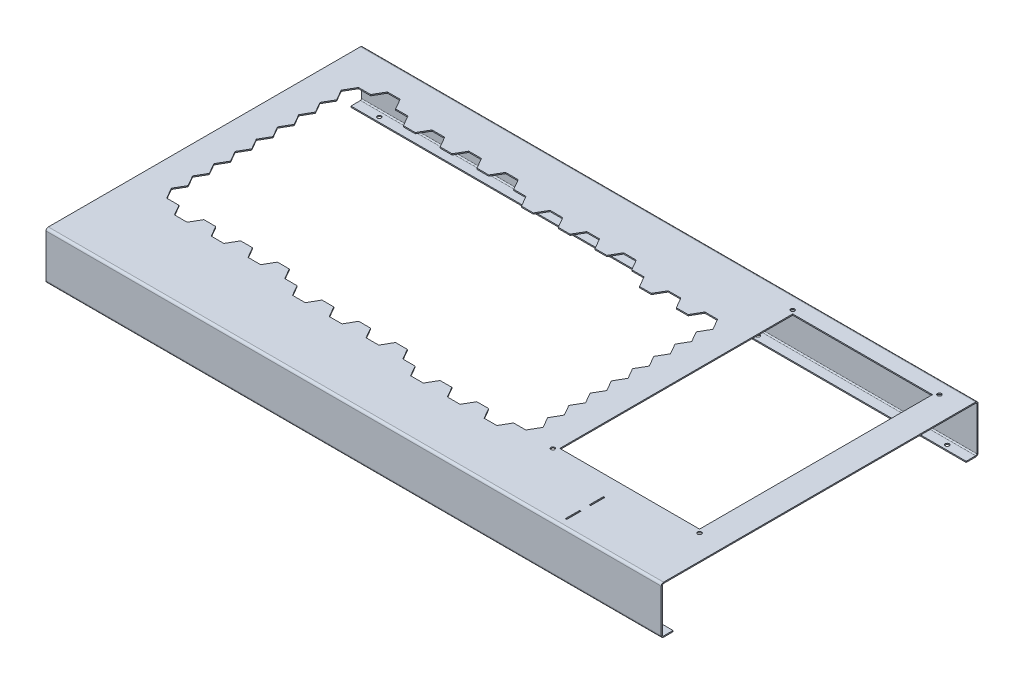
SolidWorks part; units mm, degrees
note: The reader was unsure of these and kept them because the rebuilt part matched: flange length of "Edge-Flange1", "Edge-Flange2".
ref_plane "Front" through (0, 0, 0) normal (0, 0, 1) x (1, 0, 0)
ref_plane "Top" through (0, 0, 0) normal (0, 1, 0) x (1, 0, 0)
ref_plane "Right" through (0, 0, 0) normal (1, 0, 0) x (0, 0, -1)
sketch "Sketch1" plane through (0, 0, 0) normal (0, 1, 0) x (1, 0, 0)
  line L1 (330.2, -170.0022) -> (-330.2, -170.0022)
  line L2 (330.2, -170.0022) -> (330.2, 170.0022)
  line L3 (330.2, 170.0022) -> (-330.2, 170.0022)
  line L4 (-330.2, -170.0022) -> (-330.2, 170.0022)
  line L5 (330.2, -170.0022) -> (-330.2, 170.0022) construction
  line L6 (330.2, 170.0022) -> (-330.2, -170.0022) construction
  point P0 (0, 0)
  dimension "D1" = 660.4
  dimension "D2" = 340.0044
sheet metal parameters "Sheet-Metal1" thickness 1.2192 parameters "D1"=1.27
base flange "Base-Flange1" sketch "Sketch1" thickness 1.2192 reverse thickness direction no parameters "D1"=1.27
sketch "Sketch4" plane through (0, 0, 0) normal (0, 1, 0) x (1, 0, 0)
  line L0 (114.8421, 105.8291) -> (121.6467, 94.0435)
  line L1 (121.6467, 94.0435) -> (115.0694, 82.6516)
  line L2 (94.6556, 94.4372) -> (101.2329, 105.8291)
  line L3 (101.2329, 105.8291) -> (114.8421, 105.8291)
  line L4 (115.0694, 82.6516) -> (121.6467, 71.2597)
  line L5 (121.6467, 71.2597) -> (115.0694, 59.8678)
  line L6 (115.0694, 59.8678) -> (121.6467, 48.4759)
  line L7 (121.6467, 48.4759) -> (115.0694, 37.084)
  line L8 (115.0694, 37.084) -> (121.6467, 25.6921)
  line L9 (121.6467, 25.6921) -> (115.0694, 14.3002)
  line L10 (115.0694, 14.3002) -> (121.6467, 2.9083)
  line L11 (121.6467, 2.9083) -> (115.0694, -8.4836)
  line L12 (115.0694, -8.4836) -> (121.6467, -19.8755)
  line L13 (121.6467, -19.8755) -> (115.0694, -31.2674)
  line L14 (115.0694, -31.2674) -> (121.6467, -42.6593)
  line L15 (121.6467, -42.6593) -> (115.0694, -54.0512)
  line L16 (121.6467, -65.4431) -> (115.0694, -76.835)
  line L17 (115.0694, -54.0512) -> (121.6467, -65.4431)
  line L18 (115.0694, -76.835) -> (121.6467, -88.2269)
  line L19 (121.6467, -88.2269) -> (114.8421, -100.0125)
  line L20 (114.8421, -100.0125) -> (101.6874, -100.0125)
  line L21 (101.6874, -100.0125) -> (95.1101, -111.4044)
  line L22 (95.1101, -111.4044) -> (81.5009, -111.4044)
  line L23 (81.5009, -111.4044) -> (74.9236, -100.0125)
  line L24 (74.9236, -100.0125) -> (62.2235, -100.0125)
  line L25 (62.2235, -100.0125) -> (55.6462, -111.4044)
  line L26 (55.6462, -111.4044) -> (42.037, -111.4044)
  line L27 (42.037, -111.4044) -> (35.4596, -100.0125)
  line L28 (35.4596, -100.0125) -> (22.7595, -100.0125)
  line L29 (16.1822, -111.4044) -> (2.573, -111.4044)
  line L30 (2.573, -111.4044) -> (-4.0043, -100.0125)
  line L31 (22.7595, -100.0125) -> (16.1822, -111.4044)
  line L32 (-4.0043, -100.0125) -> (-17.159, -100.0125)
  line L33 (-17.159, -100.0125) -> (-23.7363, -88.6206)
  line L34 (-23.7363, -88.6206) -> (-36.4365, -88.6206)
  line L35 (-43.0138, -100.0125) -> (-56.623, -100.0125)
  line L36 (-56.623, -100.0125) -> (-63.2003, -88.6206)
  line L37 (-36.4365, -88.6206) -> (-43.0138, -100.0125)
  line L38 (-63.2003, -88.6206) -> (-75.9005, -88.6206)
  line L39 (-82.4778, -100.0125) -> (-96.087, -100.0125)
  line L40 (-96.087, -100.0125) -> (-102.6643, -88.6206)
  line L41 (-75.9005, -88.6206) -> (-82.4778, -100.0125)
  line L42 (-121.9418, -100.0125) -> (-135.551, -100.0125)
  line L43 (-135.551, -100.0125) -> (-142.1283, -88.6206)
  line L44 (-115.3644, -88.6206) -> (-121.9418, -100.0125)
  line L45 (-142.1283, -88.6206) -> (-155.2829, -88.6206)
  line L46 (-155.2829, -88.6206) -> (-161.8603, -77.2287)
  line L47 (-161.8603, -77.2287) -> (-174.5604, -77.2287)
  line L48 (-181.1377, -88.6206) -> (-194.7469, -88.6206)
  line L49 (-194.7469, -88.6206) -> (-201.3242, -77.2287)
  line L50 (-174.5604, -77.2287) -> (-181.1377, -88.6206)
  line L51 (-201.3242, -77.2287) -> (-214.0244, -77.2287)
  line L52 (-220.6017, -88.6206) -> (-234.2109, -88.6206)
  line L53 (-234.2109, -88.6206) -> (-240.7882, -77.2287)
  line L54 (-214.0244, -77.2287) -> (-220.6017, -88.6206)
  line L55 (-240.7882, -77.2287) -> (-253.4884, -77.2287)
  line L56 (-260.0657, -88.6206) -> (-273.6749, -88.6206)
  line L57 (-273.6749, -88.6206) -> (-280.2522, -77.2287)
  line L58 (-253.4884, -77.2287) -> (-260.0657, -88.6206)
  line L59 (-280.2522, -77.2287) -> (-293.398, -77.2287)
  line L60 (-293.398, -77.2287) -> (-300.2026, -65.4431)
  line L61 (-300.2026, -65.4431) -> (-293.6253, -54.0512)
  line L62 (-293.6253, -54.0512) -> (-300.2026, -42.6593)
  line L63 (-300.2026, -42.6593) -> (-293.6253, -31.2674)
  line L64 (-293.6253, -31.2674) -> (-300.2026, -19.8755)
  line L65 (-300.2026, -19.8755) -> (-293.6253, -8.4836)
  line L66 (-300.2026, 2.9083) -> (-293.6253, 14.3002)
  line L67 (-293.6253, -8.4836) -> (-300.2026, 2.9083)
  line L68 (-293.6253, 14.3002) -> (-300.2026, 25.6921)
  line L69 (-300.2026, 25.6921) -> (-293.6253, 37.084)
  line L70 (-293.6253, 37.084) -> (-300.2026, 48.4759)
  line L71 (-300.2026, 48.4759) -> (-293.6253, 59.8678)
  line L72 (-293.6253, 59.8678) -> (-300.2026, 71.2597)
  line L73 (-300.2026, 71.2597) -> (-293.6253, 82.6516)
  line L74 (-293.6253, 82.6516) -> (-300.2026, 94.0435)
  line L75 (-300.2026, 94.0435) -> (-293.6253, 105.4354)
  line L76 (-293.6253, 105.4354) -> (-300.2026, 116.8273)
  line L77 (-300.2026, 116.8273) -> (-293.398, 128.6129)
  line L78 (-293.398, 128.6129) -> (-280.2522, 128.6129)
  line L79 (-273.6749, 140.0048) -> (-260.0657, 140.0048)
  line L80 (-260.0657, 140.0048) -> (-253.4884, 128.6129)
  line L81 (-280.2522, 128.6129) -> (-273.6749, 140.0048)
  line L82 (-253.4884, 128.6129) -> (-240.3337, 128.6129)
  line L83 (-240.3337, 128.6129) -> (-233.7564, 117.221)
  line L84 (-233.7564, 117.221) -> (-221.0562, 117.221)
  line L85 (-214.4789, 128.6129) -> (-200.8697, 128.6129)
  line L86 (-200.8697, 128.6129) -> (-194.2924, 117.221)
  line L87 (-221.0562, 117.221) -> (-214.4789, 128.6129)
  line L88 (-194.2924, 117.221) -> (-181.5922, 117.221)
  line L89 (-175.0149, 128.6129) -> (-161.4057, 128.6129)
  line L90 (-161.4057, 128.6129) -> (-154.8284, 117.221)
  line L91 (-181.5922, 117.221) -> (-175.0149, 128.6129)
  line L92 (-154.8284, 117.221) -> (-142.1283, 117.221)
  line L93 (-135.551, 128.6129) -> (-121.9418, 128.6129)
  line L94 (-121.9418, 128.6129) -> (-115.3644, 117.221)
  line L95 (-142.1283, 117.221) -> (-135.551, 128.6129)
  line L96 (-115.3644, 117.221) -> (-102.2098, 117.221)
  line L97 (-102.2098, 117.221) -> (-95.6325, 105.8291)
  line L98 (-95.6325, 105.8291) -> (-82.9323, 105.8291)
  line L99 (-76.355, 117.221) -> (-62.7458, 117.221)
  line L100 (-62.7458, 117.221) -> (-56.1685, 105.8291)
  line L101 (-82.9323, 105.8291) -> (-76.355, 117.221)
  line L102 (-56.1685, 105.8291) -> (-43.4683, 105.8291)
  line L103 (-36.891, 117.221) -> (-23.2818, 117.221)
  line L104 (-23.2818, 117.221) -> (-16.7045, 105.8291)
  line L105 (-43.4683, 105.8291) -> (-36.891, 117.221)
  line L106 (-16.7045, 105.8291) -> (-4.0043, 105.8291)
  line L107 (2.573, 117.221) -> (16.1822, 117.221)
  line L108 (16.1822, 117.221) -> (22.7595, 105.8291)
  line L109 (-4.0043, 105.8291) -> (2.573, 117.221)
  line L110 (22.7595, 105.8291) -> (35.9142, 105.8291)
  line L111 (35.9142, 105.8291) -> (42.4915, 94.4372)
  line L112 (42.4915, 94.4372) -> (55.1916, 94.4372)
  line L113 (61.7689, 105.8291) -> (75.3781, 105.8291)
  line L114 (75.3781, 105.8291) -> (81.9555, 94.4372)
  line L115 (55.1916, 94.4372) -> (61.7689, 105.8291)
  line L116 (81.9555, 94.4372) -> (94.6556, 94.4372)
  line L117 (-102.6643, -88.6206) -> (-115.3644, -88.6206)
  line L128 (-330.2, 170.0022) -> (-330.2, -170.0022) construction
  dimension "D1" = 29.9974
extrude "Cut-Extrude1" cut sketch "Sketch4" against normal through all normal cut yes
sketch "Sketch5" plane through (0, 0, 0) normal (0, 1, 0) x (1, 0, 0)
  line L0 (330.2, -170.0022) -> (330.2, 170.0022) construction
  line L1 (150.1902, 151.13) -> (300.2026, 151.13)
  line L2 (150.1902, 151.13) -> (150.1902, -98.8822)
  line L3 (150.1902, -98.8822) -> (300.2026, -98.8822)
  line L4 (300.2026, 151.13) -> (300.2026, -98.8822)
  line L5 (330.2, 170.0022) -> (-330.2, 170.0022) construction
  dimension "D1" = 150.0124
  dimension "D2" = 250.0122
  dimension "D3" = 29.9974
  dimension "D4" = 18.8722
extrude "Cut-Extrude2" cut sketch "Sketch5" against normal blind 1.2192 normal cut yes
edge flange "Edge-Flange1" sketch "Sketch10" flange profiles "Sketch10", "Sketch11" flange angle 90 flange length 50.0126 flange position material inside bend radius 1.27 thickness 1.2192 parameters "D6"=10, "D8"=1
sketch "Sketch10" plane through (0, -1.2192, -170.0022) normal (0, 0, -1) x (1, 0, 0)
  line L0 (330.2, 0) -> (-330.2, 0) construction
  line L1 (330.2, 0) -> (-330.2, 0)
  line L2 (-330.2, 0) -> (-330.2, 48.7934)
  line L3 (-330.2, 48.7934) -> (330.2, 48.7934)
  line L4 (330.2, 48.7934) -> (330.2, 0)
sketch "Sketch11" plane through (0, -1.2192, 170.0022) normal (0, 0, 1) x (-1, 0, 0)
  line L0 (330.2, 0) -> (-330.2, 0) construction
  line L1 (330.2, 0) -> (-330.2, 0)
  line L2 (-330.2, 0) -> (-330.2, 48.7934)
  line L3 (-330.2, 48.7934) -> (330.2, 48.7934)
  line L4 (330.2, 48.7934) -> (330.2, 0)
bend "EdgeBend1" bend radius 1.27 bend angle 90 parameters "D5"=1
bend "EdgeBend2" bend radius 1.27 bend angle 90 parameters "D5"=2
edge flange "Edge-Flange2" sketch "Sketch16" flange profiles "Sketch16", "Sketch17" flange angle 90 flange length 12.7 flange position material outside bend radius 1.27 thickness 1.2192 parameters "D6"=10, "D8"=1
sketch "Sketch16" plane through (0, -50.0126, -168.783) normal (0, -1, 0) x (1, 0, 0)
  line L2 (-330.2, 0) -> (-330.2, 11.4808)
  line L3 (-330.2, 11.4808) -> (330.2, 11.4808)
  line L4 (330.2, 11.4808) -> (330.2, 0)
  line L5 (330.2, 0) -> (-330.2, 0) construction
  line L6 (330.2, 0) -> (-330.2, 0)
sketch "Sketch17" plane through (0, -50.0126, 168.783) normal (0, -1, 0) x (-1, 0, 0)
  line L0 (330.2, 0) -> (-330.2, 0) construction
  line L1 (330.2, 0) -> (-330.2, 0)
  line L2 (-330.2, 0) -> (-330.2, 11.4808)
  line L3 (-330.2, 11.4808) -> (330.2, 11.4808)
  line L4 (330.2, 11.4808) -> (330.2, 0)
bend "EdgeBend3" bend radius 1.27 bend angle 90 parameters "D5"=3
bend "EdgeBend4" bend radius 1.27 bend angle 90 parameters "D5"=4
sketch "Sketch18" plane through (0, -51.2318, 0) normal (0, -1, 0) x (1, 0, 0)
  line L0 (330.2, 162.4076) -> (192.4461, 162.4076) construction
  line L2 (330.2, 157.3022) -> (330.2, 167.513) construction
  circle A0 centre (304.8, 162.4076) radius 2.1082
  dimension "D1" = 4.2164
  dimension "D2" = 25.4
extrude "Cut-Extrude3" cut sketch "Sketch18" against normal blind 1.2192 normal cut yes
pattern_linear "LPattern1" count 4 spacing 203.2 along (-1, 0, 0) of "Cut-Extrude3"
mirror "Mirror1" about plane through (0, 0, 0) normal (0, 0, 1) of "LPattern1", "Cut-Extrude3"
sketch "Sketch19" plane through (0, 0, 0) normal (0, 1, 0) x (1, 0, 0)
  line L0 (150.1902, 151.13) -> (153.1602, 148.16) construction
  line L1 (300.2026, 151.13) -> (150.1902, 151.13) construction
  line L2 (225.1964, 151.13) -> (225.1964, -138.0133) construction
  line L3 (150.1902, 26.1239) -> (300.2026, 26.1239) construction
  line L4 (150.1902, 151.13) -> (150.1902, -98.8822) construction
  line L5 (300.2026, -98.8822) -> (300.2026, 151.13) construction
  circle A0 centre (146.4544, 154.8658) radius 2.1082
  circle A1 centre (303.9384, 154.8658) radius 2.1082
  circle A2 centre (303.9384, -102.618) radius 2.1082
  circle A3 centre (146.4544, -102.618) radius 2.1082
  dimension "D2" = 4.2164
  dimension "D1" = 5.2832
  dimension "D3" = 135
extrude "Cut-Extrude4" cut sketch "Sketch19" against normal blind 1.2192 normal cut yes
sketch "Sketch20" plane through (0, 0, 0) normal (0, 1, 0) x (1, 0, 0)
  line L0 (-330.2, -170.0022) -> (330.2, -170.0022) construction
  line L1 (-304.8, -117.7544) -> (210.82, -117.7544)
  line L2 (-304.8, -117.7544) -> (-304.8, -138.0744)
  line L3 (-304.8, -138.0744) -> (210.82, -138.0744)
  line L4 (210.82, -117.7544) -> (210.82, -138.0744)
  line L5 (-304.8, -163.6522) -> (210.82, -163.6522)
  line L6 (-304.8, -163.6522) -> (-304.8, -143.3322)
  line L7 (-304.8, -143.3322) -> (210.82, -143.3322)
  line L8 (210.82, -163.6522) -> (210.82, -143.3322)
  line L11 (81.5009, -111.4044) -> (95.1101, -111.4044) construction
  line L12 (-330.2, 167.513) -> (-330.2, -167.513) construction
  dimension "D1" = 515.62
  dimension "D2" = 20.32
  dimension "D3" = 6.35
  dimension "D4" = 6.35
  dimension "D5" = 25.4
sketch "Sketch21" plane through (0, 0, 0) normal (0, 1, 0) x (1, 0, 0)
  line L0 (210.82, -127.9144) -> (246.0274, -127.9144) construction
  line L1 (218.44, -120.2944) -> (219.964, -120.2944)
  line L2 (218.44, -120.2944) -> (218.44, -135.5344)
  line L3 (218.44, -135.5344) -> (219.964, -135.5344)
  line L4 (219.964, -120.2944) -> (219.964, -135.5344)
  line L5 (218.44, -145.8722) -> (219.964, -145.8722)
  line L6 (218.44, -145.8722) -> (218.44, -161.1122)
  line L7 (218.44, -161.1122) -> (219.964, -161.1122)
  line L8 (219.964, -145.8722) -> (219.964, -161.1122)
  line L9 (210.82, -117.7544) -> (210.82, -138.0744) construction
  line L10 (210.82, -153.4922) -> (244.3879, -153.4922) construction
  line L11 (210.82, -163.6522) -> (210.82, -143.3322) construction
  dimension "D1" = 15.24
  dimension "D2" = 1.524
  dimension "D3" = 7.62
extrude "Cut-Extrude5" cut sketch "Sketch21" against normal blind 1.2192 normal cut yes
flat pattern "Flat-Pattern1" [suppressed]
sketch "Bend-Lines1" plane through (0, -1.2192, 0) normal (0, -1, 0) x (1, 0, 0)
  line L0 (-330.2, 218.1951) -> (330.2, 218.1951) construction
  line L1 (330.2, -218.1951) -> (-330.2, -218.1951) construction
  line L2 (-330.2, 168.9892) -> (330.2, 168.9892) construction
  line L3 (330.2, -168.9892) -> (-330.2, -168.9892) construction
  line L4 (-330.2, 218.1951) -> (330.2, 218.1951) construction
  line L5 (330.2, -218.1951) -> (-330.2, -218.1951) construction
  line L6 (-330.2, 168.9892) -> (330.2, 168.9892) construction
  line L7 (330.2, -168.9892) -> (-330.2, -168.9892) construction
sketch3d "Bounding-Box1" [suppressed]
  line L0 (660.4, 399.8843, 0) -> (0, 399.8843, 0) construction
  line L1 (660.4, -59.8799, 0) -> (0, -59.8799, 0) construction
  line L2 (660.4, 399.8843, 0) -> (660.4, -59.8799, 0) construction
  line L3 (0, 399.8843, 0) -> (0, -59.8799, 0) construction
bend of the flat pattern "Flatten-<EdgeBend1>1"
bend of the flat pattern "Flatten-<EdgeBend2>1"
bend of the flat pattern "Flatten-<EdgeBend3>1"
bend of the flat pattern "Flatten-<EdgeBend4>1"
